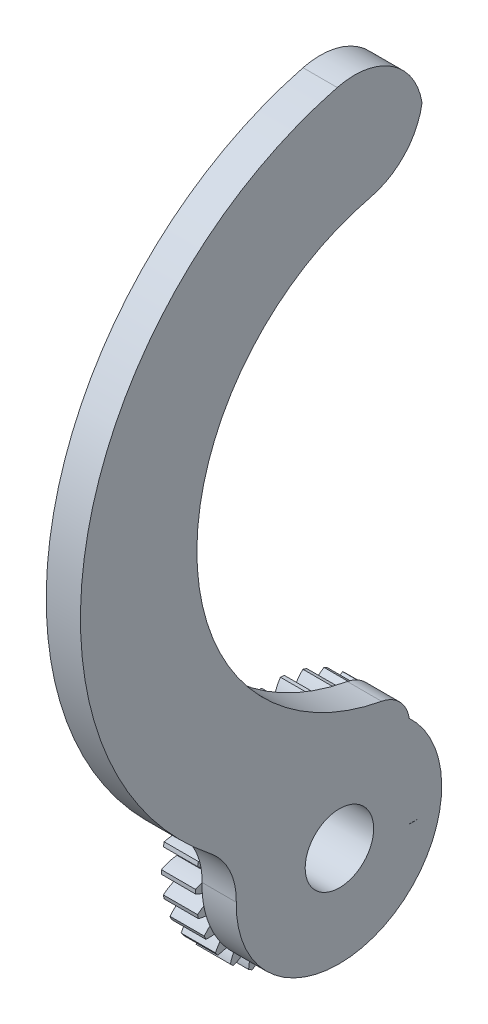
SolidWorks part; units mm, degrees
ref_plane "Plane1" through (0, 0, 0) normal (0, 0, 1) x (1, 0, 0)
ref_plane "Plane2" through (0, 0, 0) normal (0, 1, 0) x (1, 0, 0)
ref_plane "Plane3" through (0, 0, 0) normal (1, 0, 0) x (0, 0, -1)
other "Configuration Table"
sketch "HoldingSke" plane through (0, 0, 0) normal (0, 1, 0) x (1, 0, 0)
  line L0 (0, 0) -> (0.866, -0.5)
  line L1 (-15, 0) -> (100, 0) construction
  line L2 (0, 0) -> (-2.1039, 2.3779)
  line L3 (0, 0) -> (-11.863, 4.5341)
  line L4 (0, 0) -> (7.479, 4.318)
  line L5 (0, 0) -> (-46.8476, -17.4728)
  line L6 (0, 0) -> (-4.1448, -2.7965)
  line L7 (-2.1039, 2.3779) -> (8.6586, 51.2059)
  line L8 (-76.2, 54.61) -> (-76.1, 54.61)
  line L9 (-71.009, 38.7566) -> (-53.1078, 45.2721)
  line L10 (-76.2, 71.12) -> (104.1128, 71.12)
  line L11 (0, 0) -> (-5, 0)
  line L12 (-76.2, 101.6) -> (-76.162, 101.6)
  line L13 (24.9733, 27.94) -> (52.9518, 28.4284)
  line L14 (24.9733, 27.94) -> (24.9743, 27.94)
  line L15 (24.9733, 27.94) -> (100.4006, 29.5858)
  line L16 (-63.627, -1) -> (-12.827, -1)
  circle A0 centre (0, 0) radius 0.4
  circle A1 centre (0, 0) radius 13.749
  circle A2 centre (0, 0) radius 37.5
  circle A3 centre (0, 0) radius 0.4
  dimension "MHD" = 27.498
  dimension "Hub_dia" = 75
  dimension "Bore" = 0.8
  dimension "MBD" = 0.8
  dimension "Num_teeth" = 30
  dimension "Pitch" = 1
  dimension "Overall_len" = 50
  dimension "Show_teeth" = 30
  dimension "Thickness" = 5
  dimension "OAL" = 50.0001
  dimension "T_dim" = 0.1
  dimension "Ap" = 20
  dimension "H" = 19.05
  dimension "Pitch_radius" = 180.3128
  dimension "Width" = 5
  dimension "Backlash" = 0.038
  dimension "Addendum_fac" = 1
  dimension "Dedendum_fac" = 1.25
  dimension "Clearance_fac" = 0.25
  dimension "Dedendum_add" = 0.001
  dimension "Module" = 1
sketch "BasProSke" plane through (0, 0, 0) normal (0, 1, 0) x (1, 0, 0)
  line L0 (-10, 0) -> (60, 0) construction
  line L1 (0, 0) -> (0, 16)
  line L2 (0, 0) -> (5, 0)
  line L3 (5, 0) -> (5, 16)
  line L4 (5, 16) -> (0, 16)
  dimension "Thickness" = 5
  dimension "Diameter" = 32
revolve "Base-Revolve" add sketch "BasProSke" angle 360 about L0
sketch "TooCutSke" plane through (0, 0, 0) normal (1, 0, 0) x (0, 0, -1)
  line L1 (0, 0) -> (0, 107) construction
  line L2 (0, 0) -> (-0.8515, 14.9758) construction
  line L3 (0, 0) -> (-3.1323, 29.8014) construction
  line L4 (-0.8515, 14.9758) -> (-1.5661, 14.9007) construction
  arc A0 (0.4664, 13.7411) -> (-0.4664, 13.7411) centre (0, 0) ccw
  arc A1 (1.3975, 15.9644) -> (-1.3975, 15.9644) centre (0, 0) ccw
  circle A2 centre (0, 0) radius 15 construction
  circle A3 centre (0, 0) radius 14.0954 construction
  arc A4 (-0.4664, 13.7411) -> (-1.3975, 15.9644) centre (-6.3534, 12.5823) ccw
  arc A5 (1.3975, 15.9644) -> (0.4664, 13.7411) centre (6.3534, 12.5823) ccw
  dimension "Root_dia" = 27.498
  dimension "Overcut_dia" = 32.0508
  dimension "Pitch_dia" = 30
  dimension "Base_dia" = 28.1908
  dimension "Flank_rad" = 6
  dimension "Half_ang" = 6
  dimension "Half_CT" = 0.7185
extrude "ToothCut" cut sketch "TooCutSke" along normal through all
fillet "Breaks" [suppressed] radius 0.02 tangent propagation no
fillet "RootFillets" [suppressed] radius 0.251
pattern_circular "TeethCuts" count 30 every 12 about axis through (-10, 0, 0) along (1, 0, 0) of "ToothCut", "RootFillets", "Breaks"
sketch "HubNeaOneSke" plane through (0, 0, 0) normal (-1, 0, 0) x (0, 0, 1)
  circle A0 centre (0, 0) radius 13.749
  dimension "Diameter" = 27.498
extrude "HubNearOne" [suppressed] add sketch "HubNeaOneSke" along normal blind 45.0001
sketch "HubNeaBotSke" plane through (0, 0, 0) normal (-1, 0, 0) x (0, 0, 1)
  circle A0 centre (0, 0) radius 13.749
  dimension "Diameter" = 27.498
extrude "HubNearBoth" [suppressed] add sketch "HubNeaBotSke" along normal blind 22.5
ref_plane "FarPln" through (5, 0, 0) normal (1, 0, 0) x (0, 0, -1)
sketch "HubFarSke" plane through (5, 0, 0) normal (1, 0, 0) x (0, 0, -1)
  circle A0 centre (0, 0) radius 13.749
  dimension "Diameter" = 27.498
extrude "HubFar" [suppressed] add sketch "HubFarSke" along normal blind 22.5
sketch "BorSke" plane through (0, 0, 0) normal (1, 0, 0) x (0, 0, -1)
  circle A0 centre (0, 0) radius 0.4
  dimension "Diameter" = 0.8
extrude "Bore" cut sketch "BorSke" along normal mid plane 100.0001
sketch "KeySke" plane through (0, 0, 0) normal (1, 0, 0) x (0, 0, -1)
  line L0 (-0.05, 0) -> (-0.05, 0.5)
  line L1 (-0.05, 0.5) -> (0.05, 0.5)
  line L2 (0.05, 0.5) -> (0.05, 0)
  line L3 (0, 0) -> (0, 34) construction
  line L4 (-0.05, 0) -> (0.05, 0)
  dimension "Offset" = 0.5
  dimension "Width" = 0.1
extrude "Keyway" [suppressed] cut sketch "KeySke" along normal mid plane 100.0001
pattern_circular "Keyway2" [suppressed] count 2 every 90 about axis through (-10, 0, 0) along (1, 0, 0) reverse direction yes
sketch "Esquisse1" plane through (5, 0, 0) normal (1, 0, 0) x (0, 0, -1)
  line L0 (12.1863, 80.9518) -> (12.1863, 97.9518)
  line L1 (12.1863, 14.9518) -> (12.1863, -2.0482)
  line L5 (-16.6324, -2.0482) -> (12.1863, -2.0482)
  line L6 (12.1863, 4.1084) -> (10.1863, 4.1084)
  line L7 (10.1863, 4.1084) -> (10.1863, 15.0125)
  line L8 (10.1863, 15.0125) -> (10.1863, -2.0482)
  circle A3 centre (-0.0626, 0.3951) radius 15
  circle A5 centre (12.1863, 47.9518) radius 50
  circle A6 centre (12.1863, 47.9518) radius 33
  dimension "D1" = 30
  dimension "D2" = 100
  dimension "D5" = 2
  dimension "D3" = 66
extrude "Boss.-Extru.1" add sketch "Esquisse1" along normal blind 5 contours A5 L5 A3 | A5 A3 L5 L8 | A3 A5 L8 L7 | L1 A5 A3 | L8 A5 L1 L6 | L1 A3 L7 L6 | A6 L0 A5 A3 L8 region at (5, 48.9842, 21.8494) region at (5, 0.2406, 8.1963) region at (5, 6.9551, 0.1323) region at (5, 7.2291, -11.1246) region at (5, 2.4003, -13.3613) region at (5, -7.3093, 0.0598) region at (5, 1.0368, -11.1874)
sketch "Esquisse2" plane through (0, 0, 0) normal (-1, 0, 0) x (0, 0, 1)
  circle A0 centre (0, 0) radius 5
  dimension "D1" = 10
extrude "Enlèv. mat.-Extru.1" cut sketch "Esquisse2" against normal through all
fillet "Congé1" radius 10 3 edges at (7.5, 5.4679, 14.1788) (7.5, 97.9518, -12.1863) (7.5, 80.9518, -12.1863)
fillet "Congé2" radius 5 1 edges at (7.5, 15.0125, -10.1863)
equation "' \"Module@HoldingSke\" = 6.35"
equation "' \"Num_teeth@HoldingSke\" = 12"
equation "' \"Ap@HoldingSke\" =  20"
equation "' \"Ap@HoldingSke\" = 20"
equation "' \"Width@HoldingSke\" = 0.5 * 25.4"
equation "' \"Hub_dia@HoldingSke\"= 1 * 25.4"
equation "' \"Hub_dia@HoldingSke\" = 1 * 25.4"
equation "' \"Overall_len@HoldingSke\" = 1.0 * 25.4"
equation "' \"Bore@HoldingSke\" = 0.75 * 25.4"
equation "' \"T_dim@HoldingSke\" = 0.1 * 25.4"
equation "' \"Width@KeySke\" = 0.25 * 25.4"
equation "' \"Show_teeth@HoldingSke\" = 13"
equation "' \"Backlash@HoldingSke\" = 0.009 * 25.4"
equation "' \"Addendum_fac@HoldingSke\" = 1.0"
equation "' \"Dedendum_fac@HoldingSke\" = 1.25"
equation "' \"Dedendum_add@HoldingSke\" = 0.00005 * 25.4"
equation "' \"Clearance_fac@HoldingSke\" = 0.25"
equation "\"Pitch@HoldingSke\" = 1 / \"Module@HoldingSke\""
equation "\"Overcut_dia@TooCutSke\" = (\"Num_teeth@HoldingSke\" + 2 * \"Addendum_fac@HoldingSke\") / \"Pitch@HoldingSke\" + 0.002 * 25.4"
equation "\"Pitch_dia@TooCutSke\" = \"Num_teeth@HoldingSke\" / \"Pitch@HoldingSke\""
equation "\"Base_dia@TooCutSke\" = \"Num_teeth@HoldingSke\" / \"Pitch@HoldingSke\" * cos((\"Ap@HoldingSke\"  * 3.14159265 / 180))"
equation "\"Root_dia@TooCutSke\" = (\"Num_teeth@HoldingSke\" + 2) / \"Pitch@HoldingSke\" - 2 * (\"Addendum_fac@HoldingSke\" + \"Dedendum_fac@HoldingSke\") / \"Pitch@HoldingSke\" - \"Dedendum_add@HoldingSke\" * 2"
equation "\"Half_ang@TooCutSke\" = 180 / \"Num_teeth@HoldingSke\""
equation "\"Half_CT@TooCutSke\" = \"Num_teeth@HoldingSke\" / \"Pitch@HoldingSke\" * sin((3.14159265 / 2 / \"Num_teeth@HoldingSke\")) / 2 - 7 * \"Backlash@HoldingSke\" / 4"
equation "\"Flank_rad@TooCutSke\" = \"Num_teeth@HoldingSke\" / \"Pitch@HoldingSke\" / 5"
equation "\"Radius@RootFillets\" = \"Clearance_fac@HoldingSke\" / \"Pitch@HoldingSke\" + \"Dedendum_add@HoldingSke\""
equation "\"Break_rad@Breaks\" = 0.02 / \"Pitch@HoldingSke\""
equation "\"Thickness@HoldingSke\" = \"Width@HoldingSke\""
equation "\"OAL@HoldingSke\" = \"Thickness@HoldingSke\""
equation "\"MHD@HoldingSke\" = (\"Num_teeth@HoldingSke\" + 2) / \"Pitch@HoldingSke\" - 2 * (\"Addendum_fac@HoldingSke\" + \"Dedendum_fac@HoldingSke\")  / \"Pitch@HoldingSke\" - \"Dedendum_add@HoldingSke\" * 2"
equation "\"MBD@HoldingSke\" = (\"Num_teeth@HoldingSke\" + 2) / \"Pitch@HoldingSke\" - 2 * (\"Addendum_fac@HoldingSke\" + \"Dedendum_fac@HoldingSke\")  / \"Pitch@HoldingSke\" - \"Dedendum_add@HoldingSke\" * 2 - 0.002 * 25.4"
equation "\"MHD@HoldingSke\" = ((sgn( \"MHD@HoldingSke\" - \"Hub_dia@HoldingSke\" )-1)*( \"MHD@HoldingSke\" - \"Hub_dia@HoldingSke\" ))/-2+ \"Hub_dia@HoldingSke\""
equation "\"MBD@HoldingSke\" = ((sgn( \"MBD@HoldingSke\" - \"Bore@HoldingSke\" )-1)*( \"MBD@HoldingSke\" - \"Bore@HoldingSke\" ))/-2+ \"Bore@HoldingSke\""
equation "\"OAL@HoldingSke\" = ((sgn( \"OAL@HoldingSke\" - \"Overall_len@HoldingSke\" )+1)*( \"OAL@HoldingSke\" - \"Overall_len@HoldingSke\" ))/2 + \"Overall_len@HoldingSke\" + 0.000002 * 25.4"
equation "\"Num_teeth@TeethCuts\" = int( \"Show_teeth@HoldingSke\" ) + 1"
equation "\"Num_teeth@TeethCuts\" = ((sgn( \"Num_teeth@TeethCuts\" - \"Num_teeth@HoldingSke\" )-1)*( \"Num_teeth@TeethCuts\" - \"Num_teeth@HoldingSke\" ))/-2+ \"Num_teeth@HoldingSke\""
equation "\"Num_teeth@TeethCuts\" = ((sgn( \"Num_teeth@TeethCuts\" - 2.0)+1)*( \"Num_teeth@TeethCuts\" - 2.0))/2 +2.0"
equation "\"Angle@TeethCuts\" = 360.0 / \"Num_teeth@HoldingSke\""
equation "\"Diameter@BasProSke\" = (\"Num_teeth@HoldingSke\" + 2 * \"Addendum_fac@HoldingSke\") / \"Pitch@HoldingSke\""
equation "\"Thickness@BasProSke\"  = \"Thickness@HoldingSke\""
equation "' \"Fillet_rad@BasProSke\" =  \"Thickness@HoldingSke\" * 0.05"
equation "' \"Fillet_rad@BasProSke\" = \"Thickness@HoldingSke\" * 0.05"
equation "\"MHD@HoldingSke\" = ((sgn( \"MHD@HoldingSke\" - \"Root_dia@TooCutSke\" )-1)*( \"MHD@HoldingSke\" - \"Root_dia@TooCutSke\" ))/-2+ \"Root_dia@TooCutSke\""
equation "\"Diameter@HubNeaOneSke\" = \"MHD@HoldingSke\""
equation "\"Length@HubNearOne\" = \"OAL@HoldingSke\" - \"Thickness@BasProSke\""
equation "\"Diameter@HubNeaBotSke\" = \"MHD@HoldingSke\""
equation "\"Length@HubNearBoth\" = ( \"OAL@HoldingSke\" - \"Thickness@BasProSke\" ) / 2.0"
equation "\"Thickness@FarPln\" = \"Thickness@BasProSke\""
equation "\"Diameter@HubFarSke\" = \"MHD@HoldingSke\""
equation "\"Length@HubFar\" = ( \"OAL@HoldingSke\" - \"Thickness@BasProSke\" ) / 2.0"
equation "\"Diameter@BorSke\" = \"MBD@HoldingSke\""
equation "\"D1@Bore\" = \"OAL@HoldingSke\" * 2.0"
equation "\"D1@Keyway\" = \"OAL@HoldingSke\" * 2.0"
equation "\"Offset@KeySke\" = \"T_dim@HoldingSke\" + \"MBD@HoldingSke\" / 2.0"
